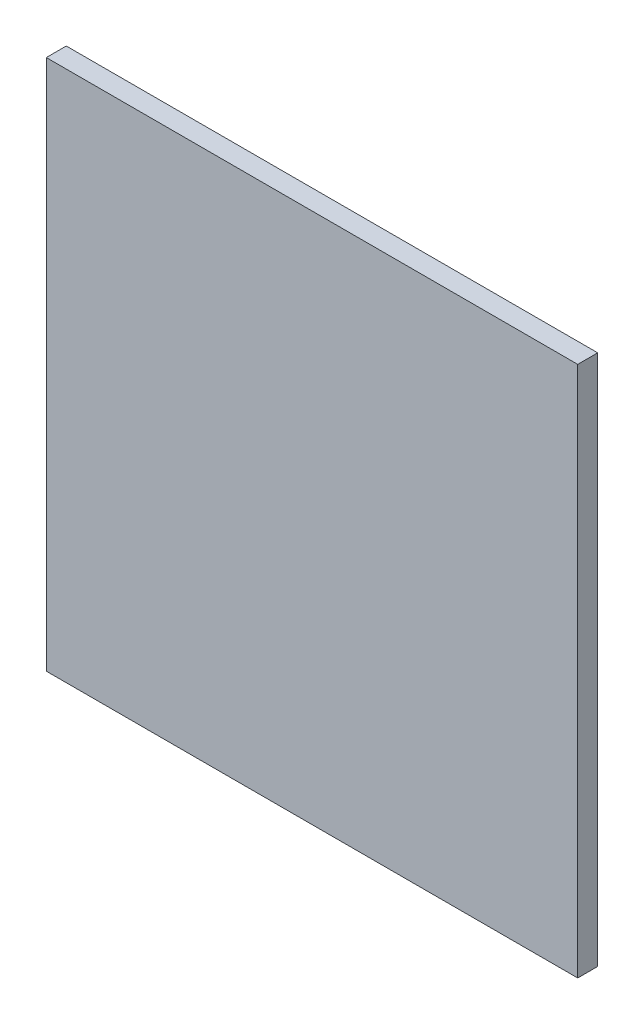
SolidWorks part; units mm, degrees
ref_plane "Přední rovina" through (0, 0, 0) normal (0, 0, 1) x (1, 0, 0)
ref_plane "Horní rovina" through (0, 0, 0) normal (0, 1, 0) x (1, 0, 0)
ref_plane "Pravá rovina" through (0, 0, 0) normal (1, 0, 0) x (0, 0, -1)
sketch "Skica1" plane through (0, 0, 0) normal (0, 0, 1) x (1, 0, 0)
  line L1 (0, 0) -> (79.8, 0)
  line L2 (0, 0) -> (0, 79.8)
  line L3 (0, 79.8) -> (79.8, 79.8)
  line L4 (79.8, 0) -> (79.8, 79.8)
  dimension "D1" = 79.8
  dimension "D2" = 79.8
extrude "Přidat vysunutím1" add sketch "Skica1" along normal blind 3
